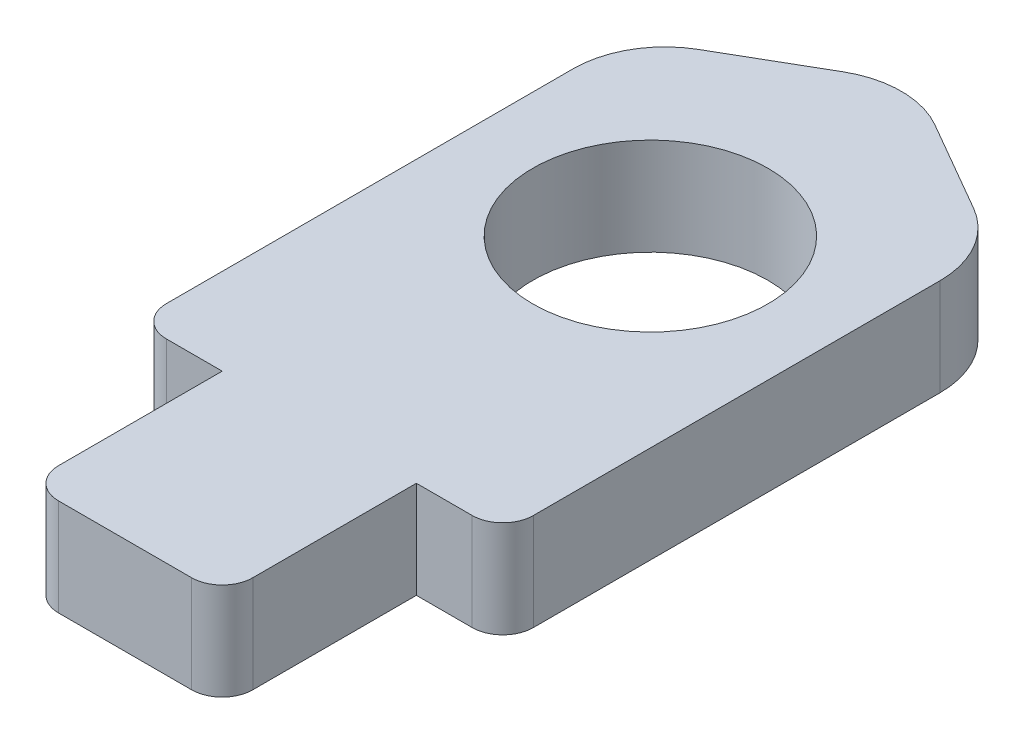
SolidWorks part; units mm, degrees
material "Beech"
ref_plane "Front Plane" through (0, 0, 0) normal (0, 0, 1) x (1, 0, 0)
ref_plane "Top Plane" through (0, 0, 0) normal (0, 1, 0) x (1, 0, 0)
ref_plane "Right Plane" through (0, 0, 0) normal (1, 0, 0) x (0, 0, -1)
sketch "Sketch2" plane through (0, 0, 0) normal (0, 1, 0) x (1, 0, 0)
  line L0 (-6, 5.205) -> (-5.4495, 5.205)
  line L1 (-6, 3.4729) -> (-6, -10.8257)
  line L2 (6, 3.4729) -> (6, -10.8257)
  line L3 (-6, -10.8257) -> (-3.175, -10.8257)
  line L4 (-4.5, 6.071) -> (-1.5, 7.8031)
  line L5 (-3.175, -10.8257) -> (-3.175, -17.1757)
  line L6 (-3.175, -17.1757) -> (3.175, -17.1757)
  line L7 (3.175, -17.1757) -> (3.175, -10.8257)
  line L8 (1.5, 7.8031) -> (4.5, 6.071)
  line L9 (3.175, -10.8257) -> (6, -10.8257)
  line L12 (5.4495, 5.205) -> (6, 5.205)
  circle A0 centre (0, 0) radius 3.845
  arc A1 (-4.5, 6.071) -> (-6, 3.4729) centre (-3, 3.4729) ccw
  arc A2 (4.5, 6.071) -> (6, 3.4729) centre (3, 3.4729) cw
  arc A3 (1.5, 7.8031) -> (-1.5, 7.8031) centre (0, 5.205) ccw
  point P3 (0, 5.205)
  point P14 (0, -17.1757)
  dimension "D1" = 7.69
  dimension "D9" = 3
  dimension "D10" = 3
  dimension "D11" = 3
  dimension "D2" = 5.205
  dimension "D3" = 16.0307
  dimension "D4" = 12
  dimension "D5" = 6.35
  dimension "D6" = 6.35
  dimension "D8" = 30
extrude "MotorMount_Extrude" add sketch "Sketch2" along normal blind 3.175 contours L8 A3 L4 A1 L1 L5 L2 A2 A0 region at (0, 0, 4.7761)
fillet "MotorMount_CornerFillet" radius 1 4 edges at (6, 1.5875, 10.8257) (-6, 1.5875, 10.8257) (-3.175, 1.5875, 17.1757) (3.175, 1.5875, 17.1757)
equation "\"CageLeftBottomEdge\"=22.11mm"
equation "\"CageLeftTopEdge\"=22.11mm"
equation "\"CageRightBottomEdge\"=21.63mm"
equation "\"CageRightTopEdge\"=21.63mm"
equation "\"CageHeight\"=86.04mm"
equation "\"CageLength\"=73.76mm"
equation "\"CageTopScrewClearance\"=10mm"
equation "\"CageBottomScrewClearance\"=25mm"
equation "\"CageLeftTopDepth\"= 11.65mm"
equation "\"CageLeftBottomDepth\"=11.11mm"
equation "\"CageLeftTopHeight\"=8.56175mm"
equation "\"CageLeftBottomHeight\"=16mm"
equation "\"CageRightTopDepth\"= 11.05mm"
equation "\"CageRightBottomDepth\"=10.58mm"
equation "\"CageRightTopHeight\"=9.6mm"
equation "\"CageRightBottomHeight\"=15.49mm"
equation "\"CageLeftTopChannelDepth\"=2.41908mm"
equation "\"CageLeftBottomChannelDepth\"=2.588mm"
equation "\"CageLeftChannelHeight\"=11.7mm"
equation "\"CageRightTopChannelDepth\"=2.32mm"
equation "\"CageRightBottomChannelDepth\"=2.318mm"
equation "\"CageRightChannelHeight\"=10mm"
equation "\"CageChanRelHeight\"=23.99mm"
equation "\"CageChanRelDepth\"=5.492mm"
equation "\"CageChamberRadius\"=16.261mm"
equation "\"CageScrewDiameter\"=4.8mm"
equation "\"CageSetScrewDiameter\"=3.5mm"
equation "\"CageAxleRadius\"=6.639mm"
equation "\"CageAxleKeyHeight\"=1.619mm"
equation "\"CageAxleKeyWidth\"=2.662mm"
equation "\"CageHoseWindowWidth\"=16.29mm"
equation "\"CageHoseWindowHeight\"=26.5mm"
equation "\"CageHoseWindow-Edge\"=8.89mm"
equation "\"CageScrew-VerticalEdge\"=5.0mm"
equation "\"CageScrew-HorizontalEdge\"=7.5mm"
equation "\"CageScrew-HoseCornerScrewEdge\"=4.45mm"
equation "\"CageAxle-BottomEdge\"=56.05mm"
equation "\"CageAxle-FrontEdge\"=46.03mm"
equation "\"CageBackSetScrew-Axle\"=40mm"
equation "\"CageFrontSetScrew-Axle\"=22mm"
equation "\"CageVelocityWindow-BackEdge\"=34.8mm"
equation "\"CageVelocityWindow-BottomEdge\"=27.55mm"
equation "\"CageVelocityWindowHeight\"=22.29mm"
equation "\"CageVelocityWindowWidth\"=12.61mm"
equation "\"TriggerSlot-BottomEdge\"=6.35mm"
equation "\"TriggerSlot-FrontEdge\"=15mm"
equation "\"TriggerSlotSize\"=6.7mm"
equation "\"TriggerRackOffset\"=.236224in"
equation "\"TriggerSlotSizeInt\"=.25in"
equation "\"MotorMountLegLength\"=.25in"
equation "\"GearOffset\"=.264907in"
equation "\"TriggerSlotSpacing\"=.25in"
equation "\"TGMGearFaceDiameter\"=24.40mm"
equation "\"TGMCylinderLength\"=15.00mm"
equation "\"TGMScrewHole-Center\"=8.70mm"
equation "\"TGMScrewHoleDiameter\"=5.04mm"
equation "\"TGMCenterHoleDiameter\"=9.50mm"
equation "\"TGMShaftCollarSideLength\"=19.00mm"
equation "\"TGMShaftCollarDockingDepth\"=7.00mm"
equation "\"whitemotordepth\"=11.27mm"
equation "\"whitemotorbackdepth\"=3.845mm"
equation "\"whitemotoraxledepth\" = 3.5mm"
equation "\"whitemotoraxleoffset\"=11.4mm"
equation "\"whitemotorwidth\"=12.07mm"
equation "\"whitemotorheight\"=16.68mm"
equation "\"whitemotorcylinderlength\" =13.04mm"
equation "\"whitemotorcylinderradius\"=3.845mm"
equation "\"whitemotorcylinderoffset\"=2.35mm"
equation "\"whitemotorcutoutlength\"=1.88mm"
equation "\"whitemotorouterrad\"=5mm"
equation "\"whitemotorinnerrad\"=2.95mm"
equation "\"D1@Sketch2\"=\"whitemotorcylinderradius\"*2"
equation "\"D2@Sketch2\"=\"whitemotoraxleoffset\"-\"whitemotorcylinderradius\"-\"whitemotorcylinderoffset\""
equation "\"D3@Sketch2\"=\"elasticdepth\"+.005in+\"TriggerRackOffset\"+\"GearOffset\""
equation "\"D5@Sketch2\"=\"TriggerSlotSizeInt\""
equation "\"D6@Sketch2\"=\"MotorMountLegLength\""
equation "\"motormountwidth\"=12mm"
equation "\"D4@Sketch2\"=\"motormountwidth\""
equation "\"TriggerMiniSlotWidth\"=3.5mm"
equation "\"TriggerRackWidth\"=6.5mm"
equation "\"elasticracklength\"=2in"
equation "\"elasticrackpegsize\"=.25in"
equation "\"elasticrackpegbuffer\"=.125in"
equation "\"elasticrackpegspacing\"=1.76476378in"
equation "\"elasticbaybuffer\"=.25in"
equation "\"elasticdepth\"=.125in"
equation "\"motormountcornerfillet\"=3mm"
equation "\"D10@Sketch2\"=\"motormountcornerfillet\""
equation "\"elasticbaydepth\"=.75in"
equation "\"pandiscradius\"=14in"
equation "\"towermaterialwidth\"=.25in"
equation "\"towerslotlength\"=.5in"
equation "\"towermarkerspace\"=5in"
equation "\"towerslothorizoffset\"=1in"
equation "\"towerslothorizspacing\"=2in"
equation "\"towerslotvertoffset\"=3in"
equation "\"towerslotvertspacing\"=2in"
equation "\"towerheight\"=12in"
equation "\"towerupslot\"=1in"
equation "\"toweraxle\"=.5in"
equation "\"towerplatslotoffset\"=1.5in"
equation "\"towermotorpanelheight\"=10in"
equation "\"towerplatdepth\"=2in"
equation "\"stepperouterrad\"=10mm"
equation "\"stepperscrewsize\"=3.45mm"
equation "\"stepperscrewc2c\"=49.5mm"
equation "\"stepperdepthoffset\"=24mm"
equation "\"stepperhorizoffset\"=22.91mm"
equation "\"shaftslotOD\"=18.8mm"
equation "\"shaftslotID\"=13.28mm"
equation "\"shaftkeywidth\"=2.67mm"
equation "\"shaftkeydepth\"=1.8mm"
equation "\"shaftcollartotaldepth\"=12.5mm"
equation "\"shaftsquaredepth\"=6mm"
equation "\"shaftsetscrewsize\"=3.5mm"
equation "\"shaftkeytightdepth\"=1.85mm"
equation "\"shaftslottightID\"=12.78mm"
equation "\"shaftsetscrewoffset\"=9mm"
equation "\"cagecollartotaldepth\"=10mm"
equation "\"cagecollartotalwidth\"=35mm"
equation "\"cagecollarbasedepth\"=4mm"
